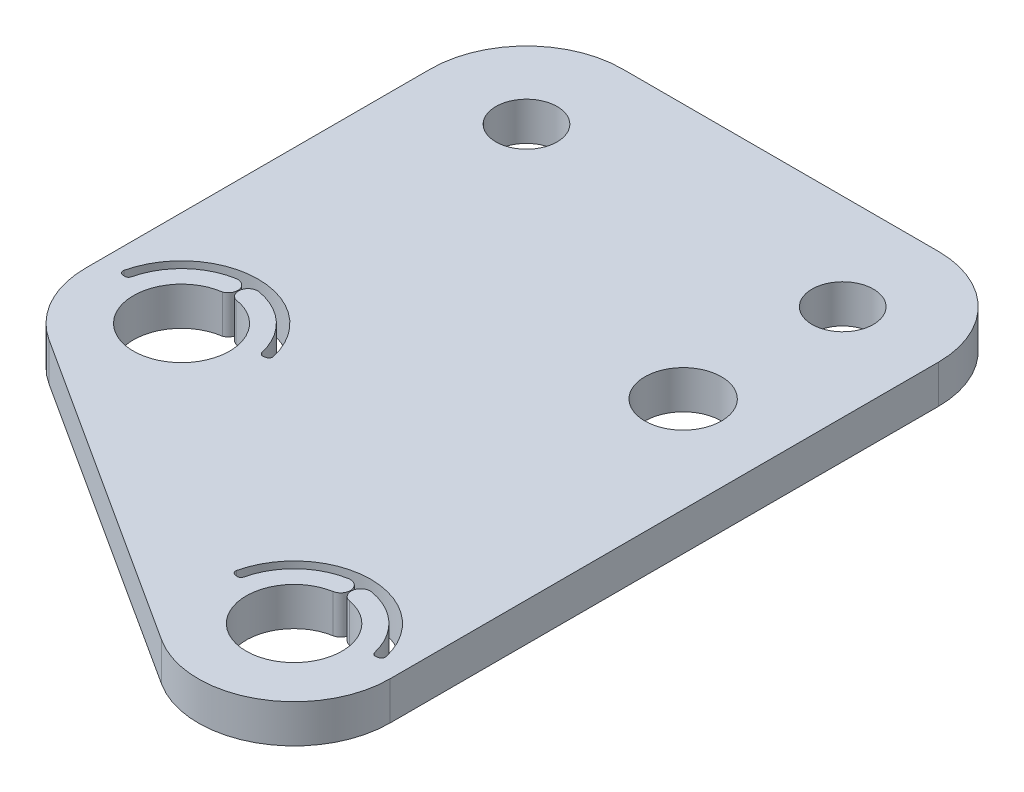
SolidWorks part; units mm, degrees
ref_plane "Front" through (0, 0, 0) normal (0, 0, 1) x (1, 0, 0)
ref_plane "Top" through (0, 0, 0) normal (0, 1, 0) x (1, 0, 0)
ref_plane "Right" through (0, 0, 0) normal (1, 0, 0) x (0, 0, -1)
sketch "Sketch1" plane through (0, 0, 0) normal (0, 1, 0) x (1, 0, 0)
  line L0 (0, 0) -> (26.5, 0)
  line L1 (26.5, 0) -> (26.5, -42.7917)
  line L2 (26.5, -42.7917) -> (0, -25.7273)
  line L3 (0, -25.7273) -> (0, 0)
  line L4 (5, -5) -> (21.5, -5) construction
  line L5 (21.5, -5) -> (21.5, -33.625) construction
  line L6 (21.5, -33.625) -> (5, -23) construction
  line L7 (5, -23) -> (5, -5) construction
  circle A0 centre (5, -23) radius 2.51
  circle A1 centre (21.5, -33.625) radius 2.5
  circle A2 centre (21.5, -5) radius 1.6
  circle A3 centre (5, -5) radius 1.6
  circle A4 centre (21.5, -13.325) radius 2
  dimension "D8" = 5.02
  dimension "D9" = 3.2
  dimension "D10" = 5
  dimension "D12" = 4
  dimension "D1" = 16.5
  dimension "D3" = 5
  dimension "D4" = 5
  dimension "D5" = 5
  dimension "D6" = 5
  dimension "D7" = 18
  dimension "D2" = 10.625
  dimension "D11" = 8.325
extrude "Boss-Extrude1" add sketch "Sketch1" along normal blind 2
fillet "Fillet1" radius 5 4 edges at (26.5, 1, 0) (0, 1, 0) (0, 1, 25.7273) (26.5, 1, 42.7917)
other "Move Face1" [suppressed] offset 0.0762 parameters "D1"=0.0762
sketch "Sketch2" plane through (0, 2, 0) normal (0, 1, 0) x (1, 0, 0)
  line B0 (17.8615, -32.9834) -> (17.7629, -32.9661)
  line B1 (25.1385, -32.9834) -> (25.2371, -32.9661)
  line B2 (20.9791, -30.6706) -> (21.5, -33.625) construction
  arc B3 (17.6028, -32.724) -> (25.3972, -32.724) centre (21.5, -33.625) cw
  arc B4 (21.0659, -31.163) -> (20.8922, -30.1782) centre (20.9791, -30.6706) ccw
  arc B5 (20.8922, -30.1782) -> (18.0911, -32.8318) centre (21.5, -33.625) ccw
  arc B6 (22.1078, -30.1782) -> (24.9089, -32.8318) centre (21.5, -33.625) cw
  arc B7 (21.9341, -31.163) -> (22.1078, -30.1782) centre (22.0209, -30.6706) cw
  arc B8 (21.0659, -31.163) -> (21.9341, -31.163) centre (21.5, -33.625) cw
  arc B9 (17.8615, -32.9834) -> (18.0911, -32.8318) centre (17.8963, -32.7865) ccw
  arc B10 (17.7629, -32.9661) -> (17.6028, -32.724) centre (17.7976, -32.7691) cw
  arc B11 (25.2371, -32.9661) -> (25.3972, -32.724) centre (25.2024, -32.7691) ccw
  arc B12 (25.1385, -32.9834) -> (24.9089, -32.8318) centre (25.1037, -32.7865) cw
  line B13 (1.3615, -22.3584) -> (1.2629, -22.3411)
  line B14 (8.6385, -22.3584) -> (8.7371, -22.3411)
  line B15 (4.4791, -20.0456) -> (5, -23) construction
  arc B16 (1.1028, -22.099) -> (8.8972, -22.099) centre (5, -23) cw
  arc B17 (4.5659, -20.538) -> (4.3922, -19.5532) centre (4.4791, -20.0456) ccw
  arc B18 (4.3922, -19.5532) -> (1.5911, -22.2068) centre (5, -23) ccw
  arc B19 (5.6078, -19.5532) -> (8.4089, -22.2068) centre (5, -23) cw
  arc B20 (5.4341, -20.538) -> (5.6078, -19.5532) centre (5.5209, -20.0456) cw
  arc B21 (4.5659, -20.538) -> (5.4341, -20.538) centre (5, -23) cw
  arc B22 (1.3615, -22.3584) -> (1.5911, -22.2068) centre (1.3963, -22.1615) ccw
  arc B23 (1.2629, -22.3411) -> (1.1028, -22.099) centre (1.2976, -22.1441) cw
  arc B24 (8.7371, -22.3411) -> (8.8972, -22.099) centre (8.7024, -22.1441) ccw
  arc B25 (8.6385, -22.3584) -> (8.4089, -22.2068) centre (8.6037, -22.1615) cw
sketch_block_instance "5mm_bore_flexure_relief-1"
sketch_block "5mm_bore_flexure_relief" parameters "D4"=2.5, "D6"=0.2, "D1"=80, "D2"=0.5, "D3"=70, "D5"=1
sketch_block_instance "5mm_bore_flexure_relief-2"
extrude "Cut-Extrude2" cut sketch "Sketch2" against normal through all
sketch "Sketch3" plane through (0, 0, 0) normal (0, 0, -1) x (-1, 0, 0)
  line L0 (-21.5, 0.4) -> (-5, 0.4) construction
  line L1 (-21.5, 2) -> (-21.5, 0) construction
  line L2 (-5, 0) -> (-5, 2) construction
  line L3 (-21.5, 0) -> (-5, 0) construction
  text T0 "MRP-01" font "Century Gothic" height in points 5
  dimension "D1" = 0.4
extrude "Cut-Extrude3" cut sketch "Sketch3" against normal blind 0.4
equation "\"D4@Sketch1\"=\"D3@Sketch1\""
equation "\"D5@Sketch1\"=\"D3@Sketch1\""
equation "\"D6@Sketch1\"=\"D3@Sketch1\""
